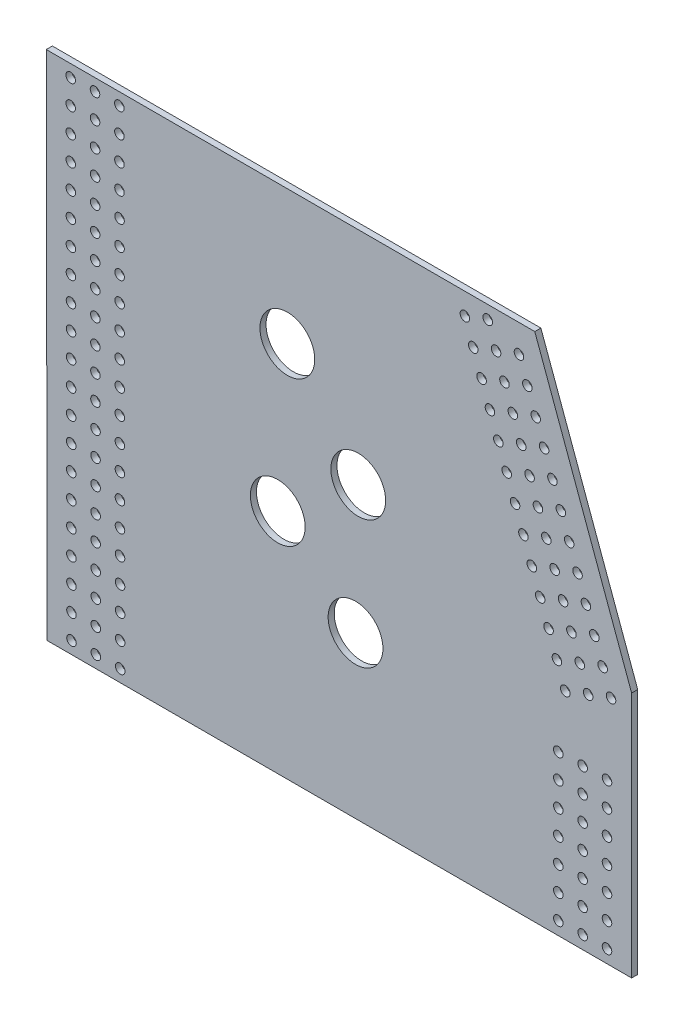
SolidWorks part; units mm, degrees
ref_plane "Front Plane" through (0, 0, 0) normal (0, 0, 1) x (1, 0, 0)
ref_plane "Top Plane" through (0, 0, 0) normal (0, 1, 0) x (1, 0, 0)
ref_plane "Right Plane" through (0, 0, 0) normal (1, 0, 0) x (0, 0, -1)
sketch "Sketch1" plane through (0, 0, 0) normal (0, 0, 1) x (1, 0, 0)
  line B0 (-0.0251, 266.6996) -> (254.7308, 266.6996)
  line B1 (0.4372, 0) -> (-0.0251, 266.6996)
  line B2 (0.4372, 0) -> (305.2377, 0)
  line B3 (305.2377, 0) -> (305.2377, 128.6779)
  line B4 (305.2377, 128.6779) -> (254.7308, 266.6996)
  circle B5 centre (25.3859, 260.3496) radius 2.4892
  circle B6 centre (38.0859, 260.3496) radius 2.4892
  circle B7 centre (25.4079, 247.6496) radius 2.4892
  circle B8 centre (125.6826, 196.681) radius 14.2875
  circle B9 centre (162.6718, 151.4627) radius 14.2875
  circle B10 centre (120.691, 118.5613) radius 14.2875
  circle B11 centre (161.2509, 83.907) radius 14.2875
  circle B12 centre (38.1079, 247.6496) radius 2.4892
  circle B13 centre (12.6859, 260.3496) radius 2.4892
  circle B14 centre (25.4299, 234.9497) radius 2.4892
  circle B15 centre (38.1299, 234.9497) radius 2.4892
  circle B16 centre (25.452, 222.2497) radius 2.4892
  circle B17 centre (38.152, 222.2497) radius 2.4892
  circle B18 centre (25.474, 209.5497) radius 2.4892
  circle B19 centre (38.174, 209.5497) radius 2.4892
  circle B20 centre (25.496, 196.8497) radius 2.4892
  circle B21 centre (38.196, 196.8497) radius 2.4892
  circle B22 centre (25.518, 184.1497) radius 2.4892
  circle B23 centre (38.218, 184.1497) radius 2.4892
  circle B24 centre (25.54, 171.4498) radius 2.4892
  circle B25 centre (38.24, 171.4498) radius 2.4892
  circle B26 centre (25.562, 158.7498) radius 2.4892
  circle B27 centre (38.262, 158.7498) radius 2.4892
  circle B28 centre (25.5841, 146.0498) radius 2.4892
  circle B29 centre (38.2841, 146.0498) radius 2.4892
  circle B30 centre (25.6061, 133.3498) radius 2.4892
  circle B31 centre (38.3061, 133.3498) radius 2.4892
  circle B32 centre (25.6281, 120.6498) radius 2.4892
  circle B33 centre (38.3281, 120.6498) radius 2.4892
  circle B34 centre (25.6501, 107.9498) radius 2.4892
  circle B35 centre (38.3501, 107.9498) radius 2.4892
  circle B36 centre (25.6721, 95.2499) radius 2.4892
  circle B37 centre (38.3721, 95.2499) radius 2.4892
  circle B38 centre (25.6941, 82.5499) radius 2.4892
  circle B39 centre (38.3941, 82.5499) radius 2.4892
  circle B40 centre (25.7162, 69.8499) radius 2.4892
  circle B41 centre (38.4162, 69.8499) radius 2.4892
  circle B42 centre (25.7382, 57.1499) radius 2.4892
  circle B43 centre (38.4382, 57.1499) radius 2.4892
  circle B44 centre (25.7602, 44.4499) radius 2.4892
  circle B45 centre (38.4602, 44.4499) radius 2.4892
  circle B46 centre (25.7822, 31.75) radius 2.4892
  circle B47 centre (38.4822, 31.75) radius 2.4892
  circle B48 centre (25.8042, 19.05) radius 2.4892
  circle B49 centre (38.5042, 19.05) radius 2.4892
  circle B50 centre (25.8262, 6.35) radius 2.4892
  circle B51 centre (38.5262, 6.35) radius 2.4892
  circle B52 centre (12.7079, 247.6496) radius 2.4892
  circle B53 centre (12.7299, 234.9497) radius 2.4892
  circle B54 centre (12.752, 222.2497) radius 2.4892
  circle B55 centre (12.774, 209.5497) radius 2.4892
  circle B56 centre (12.796, 196.8497) radius 2.4892
  circle B57 centre (12.818, 184.1497) radius 2.4892
  circle B58 centre (12.84, 171.4498) radius 2.4892
  circle B59 centre (12.862, 158.7498) radius 2.4892
  circle B60 centre (12.8841, 146.0498) radius 2.4892
  circle B61 centre (12.9061, 133.3498) radius 2.4892
  circle B62 centre (12.9281, 120.6498) radius 2.4892
  circle B63 centre (12.9501, 107.9498) radius 2.4892
  circle B64 centre (12.9721, 95.2499) radius 2.4892
  circle B65 centre (12.9941, 82.5499) radius 2.4892
  circle B66 centre (13.0162, 69.8499) radius 2.4892
  circle B67 centre (13.0382, 57.1499) radius 2.4892
  circle B68 centre (13.0602, 44.4499) radius 2.4892
  circle B69 centre (13.0822, 31.75) radius 2.4892
  circle B70 centre (13.1042, 19.05) radius 2.4892
  circle B71 centre (13.1262, 6.35) radius 2.4892
  circle B72 centre (218.2671, 255.4759) radius 2.4892
  circle B73 centre (222.6314, 243.5493) radius 2.4892
  circle B74 centre (226.9958, 231.6228) radius 2.4892
  circle B75 centre (231.3601, 219.6962) radius 2.4892
  circle B76 centre (235.7244, 207.7697) radius 2.4892
  circle B77 centre (240.0888, 195.8431) radius 2.4892
  circle B78 centre (244.4531, 183.9166) radius 2.4892
  circle B79 centre (248.8175, 171.99) radius 2.4892
  circle B80 centre (253.1818, 160.0635) radius 2.4892
  circle B81 centre (257.5461, 148.1369) radius 2.4892
  circle B82 centre (261.9105, 136.2104) radius 2.4892
  circle B83 centre (266.2748, 124.2838) radius 2.4892
  circle B84 centre (270.6391, 112.3573) radius 2.4892
  circle B85 centre (230.1936, 259.8402) radius 2.4892
  circle B86 centre (246.4845, 252.278) radius 2.4892
  circle B87 centre (234.558, 247.9137) radius 2.4892
  circle B88 centre (238.9223, 235.9871) radius 2.4892
  circle B89 centre (243.2867, 224.0606) radius 2.4892
  circle B90 centre (247.651, 212.134) radius 2.4892
  circle B91 centre (252.0153, 200.2075) radius 2.4892
  circle B92 centre (256.3797, 188.2809) radius 2.4892
  circle B93 centre (260.744, 176.3544) radius 2.4892
  circle B94 centre (265.1083, 164.4278) radius 2.4892
  circle B95 centre (269.4727, 152.5013) radius 2.4892
  circle B96 centre (273.837, 140.5747) radius 2.4892
  circle B97 centre (278.2014, 128.6482) radius 2.4892
  circle B98 centre (282.5657, 116.7216) radius 2.4892
  circle B99 centre (250.8489, 240.3514) radius 2.4892
  circle B100 centre (255.2132, 228.4249) radius 2.4892
  circle B101 centre (259.5775, 216.4984) radius 2.4892
  circle B102 centre (263.9419, 204.5718) radius 2.4892
  circle B103 centre (268.3062, 192.6453) radius 2.4892
  circle B104 centre (272.6706, 180.7187) radius 2.4892
  circle B105 centre (277.0349, 168.7922) radius 2.4892
  circle B106 centre (281.3992, 156.8656) radius 2.4892
  circle B107 centre (285.7636, 144.9391) radius 2.4892
  circle B108 centre (290.1279, 133.0125) radius 2.4892
  circle B109 centre (294.4922, 121.086) radius 2.4892
  circle B110 centre (266.9938, 82.9902) radius 2.4892
  circle B111 centre (279.6938, 82.9902) radius 2.4892
  circle B112 centre (292.3938, 82.9902) radius 2.4892
  circle B113 centre (279.6938, 70.2902) radius 2.4892
  circle B114 centre (292.3938, 70.2902) radius 2.4892
  circle B115 centre (279.6938, 57.5902) radius 2.4892
  circle B116 centre (292.3938, 57.5902) radius 2.4892
  circle B117 centre (279.6938, 44.8902) radius 2.4892
  circle B118 centre (292.3938, 44.8902) radius 2.4892
  circle B119 centre (279.6938, 32.1902) radius 2.4892
  circle B120 centre (292.3938, 32.1902) radius 2.4892
  circle B121 centre (279.6938, 19.4902) radius 2.4892
  circle B122 centre (292.3938, 19.4902) radius 2.4892
  circle B123 centre (279.6938, 6.7902) radius 2.4892
  circle B124 centre (292.3938, 6.7902) radius 2.4892
  circle B125 centre (266.9938, 70.2902) radius 2.4892
  circle B126 centre (266.9938, 57.5902) radius 2.4892
  circle B127 centre (266.9938, 44.8902) radius 2.4892
  circle B128 centre (266.9938, 32.1902) radius 2.4892
  circle B129 centre (266.9938, 19.4902) radius 2.4892
  circle B130 centre (266.9938, 6.7902) radius 2.4892
  circle B131 centre (196.0489, 55.3411) radius 9.525
  circle B132 centre (126.4529, 55.3411) radius 9.525
  circle B133 centre (221.4489, 55.3411) radius 2.4892
  circle B134 centre (208.7489, 33.3441) radius 2.4892
  circle B135 centre (183.3489, 33.3441) radius 2.4892
  circle B136 centre (170.6489, 55.3411) radius 2.4892
  circle B137 centre (183.3489, 77.3382) radius 2.4892
  circle B138 centre (208.7489, 77.3382) radius 2.4892
  circle B139 centre (101.0529, 55.3411) radius 2.4892
  circle B140 centre (113.7529, 77.3382) radius 2.4892
  circle B141 centre (139.1529, 77.3382) radius 2.4892
  circle B142 centre (151.8529, 55.3411) radius 2.4892
  circle B143 centre (139.1529, 33.3441) radius 2.4892
  circle B144 centre (113.7529, 33.3441) radius 2.4892
  circle B145 centre (179.3164, 170.656) radius 2.4892
  circle B146 centre (146.0134, 132.2952) radius 2.4892
sketch_block_instance "Block-Plate1-1"
sketch_block "Block-Plate1" parameters "D1"=28.575, "D2"=28.575, "D3"=28.575, "D4"=28.575, "D8"=4.9784, "D12"=4.9784, "D16"=19.05, "D17"=19.05, "D18"=4.9784, "D22"=4.9784, "D24"=4.9784, "D25"=4.9784, "D5"=12.7, "D6"=12.7, "D7"=12.7, "D9"=12.7, "D10"=12.7, "D11"=12.7, "D13"=12.7, "D14"=12.7, "D15"=6.7902, "D19"=25.4, "D20"=25.4, "D21"=25.4, "D23"=25.4
extrude "Boss-Extrude1" add sketch "Sketch1" along normal blind 3.175
sketch "Sketch2" plane through (0, 0, 3.175) normal (0, 0, 1) x (1, 0, 0)
  circle A0 centre (126.4529, 55.3411) radius 29.21
  circle A1 centre (196.0489, 55.3411) radius 29.21
  circle A2 centre (179.3164, 170.656) radius 2.4892
  circle A3 centre (146.0134, 132.2952) radius 2.4892
  circle A5 centre (126.4529, 55.3411) radius 9.525 construction
  dimension "D1" = 4.9784
  dimension "D2" = 4.9784
  dimension "D3" = 58.42
  dimension "D4" = 58.42
extrude "Boss-Extrude2" add sketch "Sketch2" against normal blind 3.175
